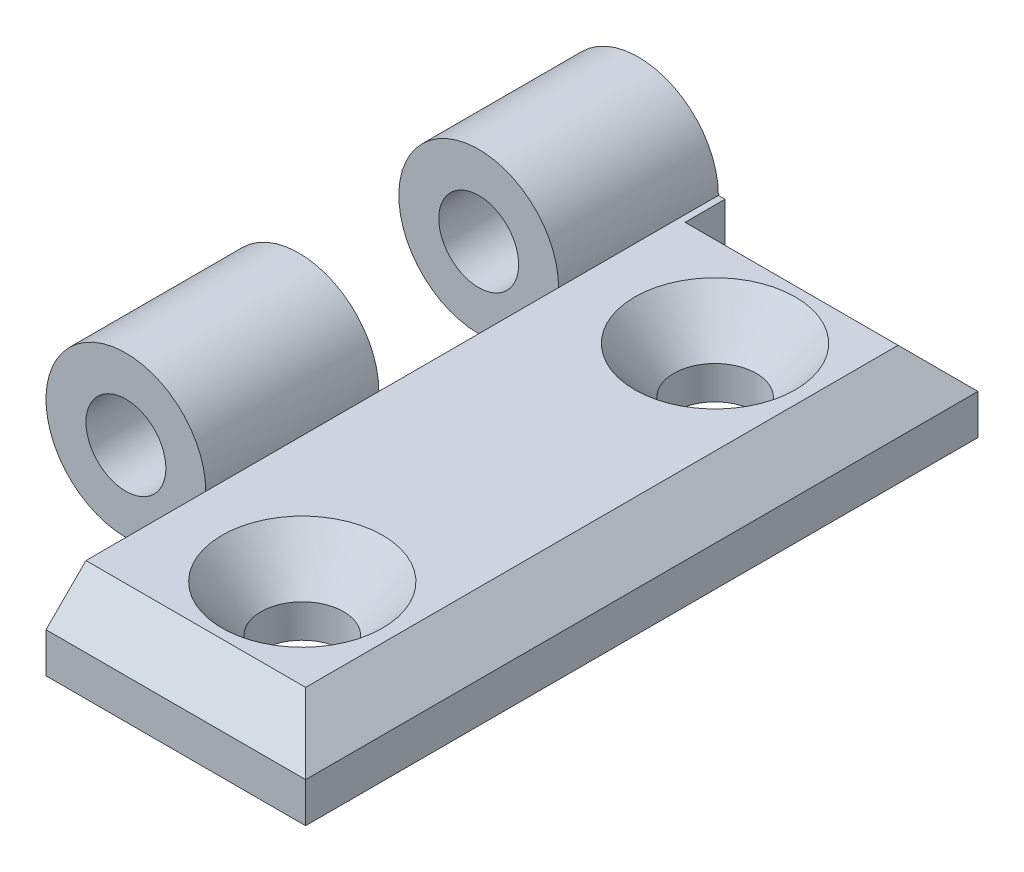
SolidWorks part; units mm, degrees
ref_plane "Спереди (XY)" through (0, 0, 0) normal (0, 0, 1) x (1, 0, 0)
ref_plane "Сверху (XZ)" through (0, 0, 0) normal (0, 1, 0) x (1, 0, 0)
ref_plane "Справа (ZY)" through (0, 0, 0) normal (1, 0, 0) x (0, 0, -1)
sketch "Эскиз1" plane through (0, 0, 0) normal (0, 0, 1) x (1, 0, 0)
  line L0 (0, 54.0796) -> (0, 0) construction
  line L1 (0, 0) -> (69.3525, 0) construction
  line L2 (25.5, 0) -> (25.5, 6)
  line L3 (25.5, 6) -> (6, 6)
  line L4 (25.5, 0) -> (0, 0)
  circle A0 centre (0, 6) radius 3
  circle A1 centre (0, 6) radius 6
  dimension "D2" = 6
  dimension "D1" = 6
  dimension "D3" = 25.5
extrude "Бобышка-Вытянуть1" add sketch "Эскиз1" along normal blind 50.5 contours A1 L4 L2 L3 | A1 A0 region at (15.0631, 2.8972, 0) region at (-4.1226, 10.1226, 0)
sketch "Эскиз3" plane through (0, 0, 0) normal (0, 1, 0) x (1, 0, 0)
  line L0 (-6, -50.5) -> (6, -50.5) construction
  line L1 (-22.1664, -58.2287) -> (6, -58.2287)
  line L2 (-22.1664, -58.2287) -> (-22.1664, -38.5)
  line L3 (-22.1664, -38.5) -> (6, -38.5)
  line L4 (6, -58.2287) -> (6, -38.5)
  line L5 (-22.6737, -25.5) -> (6, -25.5)
  line L6 (-22.6737, -25.5) -> (-22.6737, -12)
  line L7 (-22.6737, -12) -> (6, -12)
  line L8 (6, -25.5) -> (6, -12)
  line L9 (6, -50.5) -> (6, 0) construction
  line L10 (15.5, 12.9179) -> (15.5, -65.4351) construction
  line L11 (25.5, -25.25) -> (10.5911, -25.25) construction
  line L12 (25.5, -50.5) -> (25.5, 0) construction
  circle A0 centre (15.5, -9.75) radius 3.1
  circle A1 centre (15.5, -40.75) radius 3.1
  dimension "D5" = 31
  dimension "D6" = 6.2
  dimension "D1" = 12
  dimension "D2" = 13.5
  dimension "D3" = 12
  dimension "D4" = 15.5
extrude "Вырез-Вытянуть2" cut sketch "Эскиз3" along normal blind 50.5 and the other way through all
sketch "Эскиз4" plane through (0, 0, 0) normal (1, 0, 0) x (0, 0, -1)
  line L0 (-3, 6) -> (0, 3)
  line L4 (0, 0) -> (0, 6)
  line L5 (0, 6) -> (-50.5, 6)
  line L6 (-50.5, 6) -> (-50.5, 0)
  line L7 (-50.5, 0) -> (0, 0)
  line L8 (0, 0) -> (0, 6)
  line L9 (0, 6) -> (-50.5, 6)
  line L10 (-50.5, 6) -> (-50.5, 0)
  line L11 (-50.5, 0) -> (0, 0)
  dimension "D2" = 3
  dimension "D3" = 3
  dimension "D1" = 0
extrude "Вырез-Вытянуть3" cut sketch "Эскиз4" along normal blind 50.5 from offset 6.5 contours L8 L9 L0 region at (0, 5, 1)
chamfer "Фаска1" distance 3 angle 45 2 edges at (15.75, 6, 50.5) (25.5, 6, 26.75)
extrude "Вырез-Вытянуть5" cut sketch "Эскиз3<2>" along normal blind 10 draft 40 from offset 2.5 contours A1 | A0 draft outward yes
sketch "Эскиз3<2>" plane through (0, 0, 0) normal (0, 1, 0) x (1, 0, 0) same geometry as "Эскиз3"
